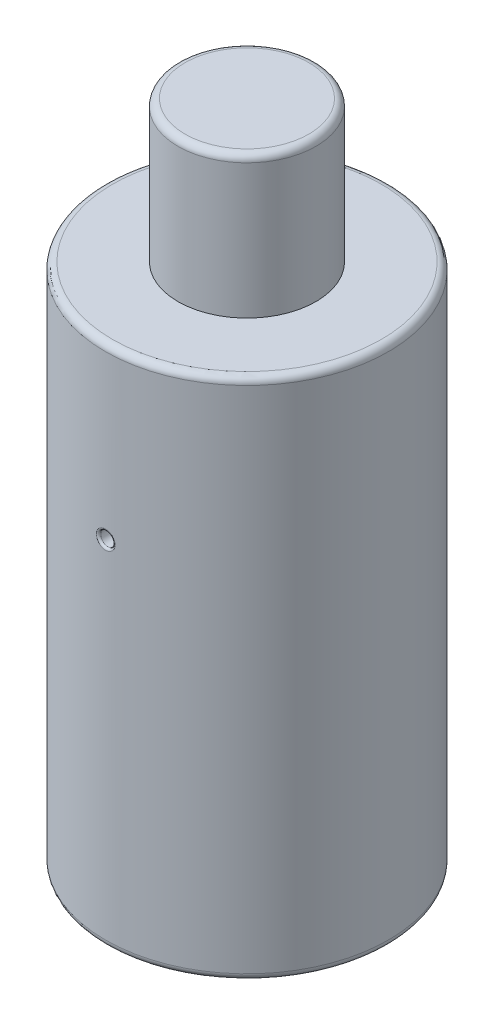
SolidWorks part; units mm, degrees
ref_plane "Front Plane" through (0, 0, 0) normal (0, 0, 1) x (1, 0, 0)
ref_plane "Top Plane" through (0, 0, 0) normal (0, 1, 0) x (1, 0, 0)
ref_plane "Right Plane" through (0, 0, 0) normal (1, 0, 0) x (0, 0, -1)
sketch "Sketch1" plane through (0, 0, 0) normal (0, 1, 0) x (1, 0, 0)
  circle A0 centre (0, 0) radius 20
  dimension "D1" = 40
extrude "Boss-Extrude1" add sketch "Sketch1" along normal blind 74
sketch "Sketch2" plane through (0, 74, 0) normal (0, 1, 0) x (1, 0, 0)
  circle A0 centre (0, 0) radius 9.75
  dimension "D1" = 19.5
extrude "Boss-Extrude2" add sketch "Sketch2" along normal blind 20
fillet "Fillet1" radius 1 3 edges at (0, 0, 20) (0, 74, 20) (0, 94, 9.75)
sketch "Sketch3" plane through (0, 0, 0) normal (0, 0, 1) x (1, 0, 0)
  line L0 (0, 0) -> (0, 50) construction
  circle A0 centre (0, 50) radius 1
  dimension "D1" = 2
  dimension "D2" = 50
extrude "Cut-Extrude1" cut sketch "Sketch3" against normal through all and the other way through all contours A0
sketch "Sketch5" plane through (0, 0, 0) normal (1, 0, 0) x (0, 0, -1)
  line L0 (0, 0) -> (0, 20) construction
  circle A0 centre (0, 20) radius 1
  spline S0 degree 2 poles (-20, 51) (-19.95, 50) (-20, 49) knots 0 0 0 1 1 1 weights 0.019 0.02 0.021 construction
  spline S1 degree 2 poles (-20, 51) (-19.95, 50) (-20, 49) knots 0 0 0 1 1 1 weights 0.019 0.02 0.021 construction
  dimension "D1" = 2
  dimension "D2" = 20
extrude "Cut-Extrude2" cut sketch "Sketch5" against normal through all
fillet "Fillet2" radius 0.3 3 edges at (-19.9987, 20.9735, 0.2286) (0.2286, 49.0265, -19.9987) (-0.9735, 50.2286, 19.9763)
ref_axis "Axis1" through (0, 50, -19.7566) along (0, 0, 1)
ref_axis "Axis2" through (-19.7566, 20, 0) along (1, 0, 0)
ref_plane "Plane1" through (0, 50, 0) normal (0, -1, 0) x (-1, 0, 0)
sketch "Sketch6" plane through (0, 50, 0) normal (0, -1, 0) x (-1, 0, 0)
  circle A0 centre (0, 0) radius 19 construction
ref_plane "Plane2" through (-20, 0, 0) normal (-1, 0, 0) x (0, 0, 1)
sketch "Sketch8" plane through (-20, 0, 0) normal (-1, 0, 0) x (0, 0, 1)
  circle A0 centre (0, 20) radius 1 construction
ref_axis "Axis3" through (0, 50, 0) along (-0.5547, -0.8321, 0)
